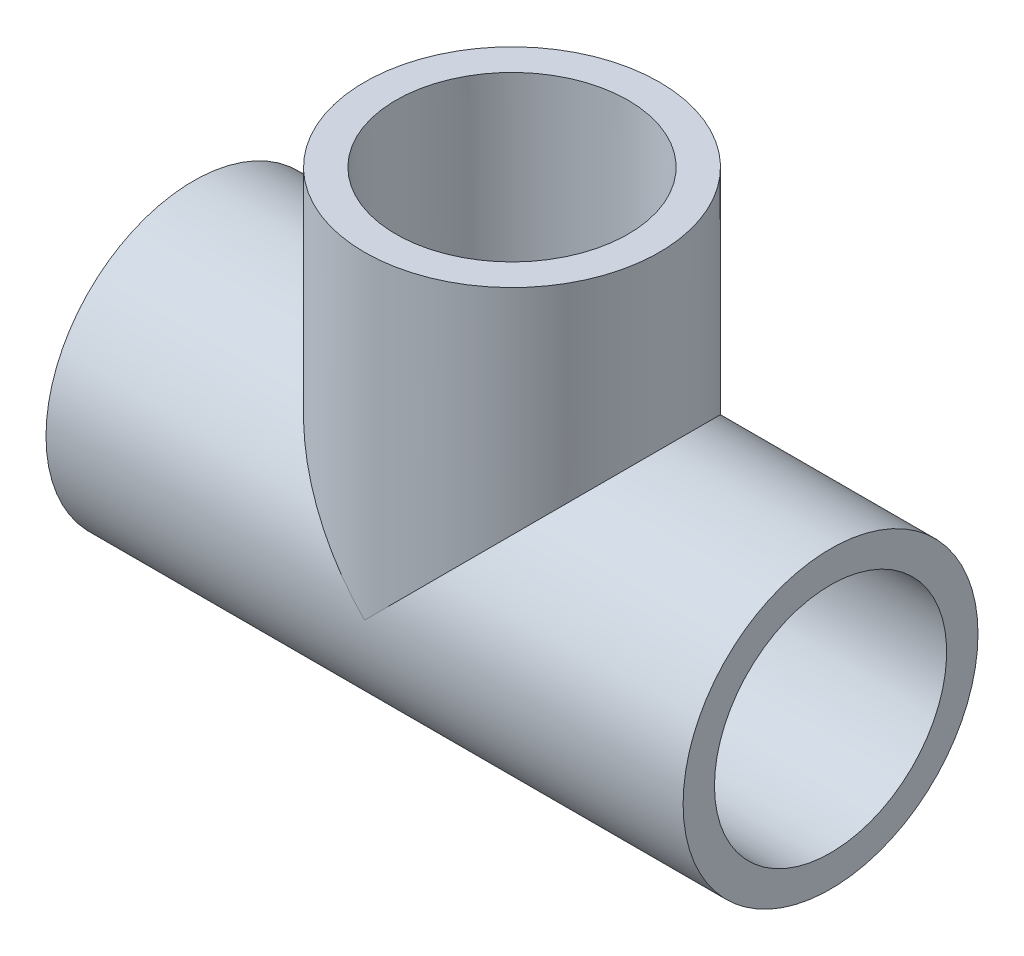
SolidWorks part; units mm, degrees
ref_plane "Front Plane" through (0, 0, 0) normal (0, 0, 1) x (1, 0, 0)
ref_plane "Top Plane" through (0, 0, 0) normal (0, 1, 0) x (1, 0, 0)
ref_plane "Right Plane" through (0, 0, 0) normal (1, 0, 0) x (0, 0, -1)
sketch "Sketch0" plane through (0, 0, 0) normal (0, 0, 1) x (1, 0, 0)
  line L0 (-46.1772, 0) -> (0, 0) construction
  line L1 (0, 0) -> (0, 46.1772) construction
  line L2 (-17.4752, 0) -> (0, 0) construction
  line L3 (0, 0) -> (0, 17.4752) construction
  line L4 (-46.1772, 21.3741) -> (-46.1772, -21.3741) construction
  line L5 (-17.4752, 16.637) -> (-46.1772, 16.8275) construction
  line L6 (-17.4752, 16.637) -> (-17.4752, -16.637) construction
  line L7 (-17.4752, -16.637) -> (-46.1772, -16.8275) construction
  line L8 (-46.1772, 16.8275) -> (-46.1772, -16.8275) construction
  line L9 (-21.3741, 46.1772) -> (21.3741, 46.1772) construction
  line L10 (-16.8275, 46.1772) -> (16.8275, 46.1772) construction
  line L11 (16.8275, 46.1772) -> (16.637, 17.4752) construction
  line L12 (16.637, 17.4752) -> (-16.637, 17.4752) construction
  line L13 (-16.637, 17.4752) -> (-16.8275, 46.1772) construction
  line L14 (-17.4752, 12.1539) -> (-17.4752, -12.1539) construction
  line L18 (-12.1539, 17.4752) -> (12.1539, 17.4752) construction
  dimension "H" = 46.1772
  dimension "G" = 17.4752
  dimension "M" = 42.7482
  dimension "OD A" = 33.655
  dimension "OD B" = 33.274
  dimension "ID" = 24.3078
sketch "Sketch1" plane through (0, 0, 0) normal (0, 0, 1) x (1, 0, 0)
  line L0 (-46.1772, 0) -> (0, 0) construction
  line L1 (-46.1772, 0) -> (0, 0) construction
  line L3 (-46.1772, -21.3741) -> (-17.4752, -21.3741)
  line L4 (-46.1772, -21.3741) -> (-46.1772, -16.8275)
  line L5 (-46.1772, -16.8275) -> (-17.4752, -16.637)
  line L6 (-17.4752, -21.3741) -> (-17.4752, -16.637)
revolve "Revolve1" add sketch "Sketch1" angle 360 about L1
mirror "Mirror1" about plane through (0, 0, 0) normal (1, 0, 0) of bodies 102
sketch "Sketch2" plane through (0, 0, 0) normal (0, 0, 1) x (1, 0, 0)
  line L0 (16.8275, 46.1772) -> (16.637, 17.4752)
  line L1 (16.637, 17.4752) -> (21.3741, 17.4752)
  line L2 (21.3741, 17.4752) -> (21.3741, 46.1772)
  line L3 (21.3741, 46.1772) -> (16.8275, 46.1772)
  line L4 (0, 0) -> (0, 46.1772) construction
  line L5 (0, 0) -> (0, 46.1772) construction
revolve "Revolve2" add sketch "Sketch2" angle 360 about L5
sketch "Sketch3" plane through (-17.4752, 0, 0) normal (1, 0, 0) x (0, 0, -1)
  line L0 (-21.3741, 17.4752) -> (21.3741, 17.4752) construction
  line L2 (12.3073, 17.4752) -> (-12.3073, 17.4752)
  circle A1 centre (0, 0) radius 21.3741 construction
  arc A3 (-12.3073, 17.4752) -> (12.3073, 17.4752) centre (0, 0) ccw
extrude "Boss-Extrude1" add sketch "Sketch3" along normal up to surface (34.9504 mm away) up to face at (17.4752, 0, 16.637)
sketch "Sketch4" plane through (0, 17.4752, 0) normal (0, -1, 0) x (1, 0, 0)
  line L0 (17.4752, -12.3073) -> (17.4752, 12.3073)
  line L1 (-17.4752, -12.3073) -> (-17.4752, 12.3073)
  circle A0 centre (0, 0) radius 21.3741 construction
  arc A1 (17.4752, 12.3073) -> (-17.4752, 12.3073) centre (0, 0) ccw
  arc A2 (-17.4752, -12.3073) -> (17.4752, -12.3073) centre (0, 0) ccw
  circle A3 centre (0, 0) radius 21.3741 construction
  circle A4 centre (0, 0) radius 21.3741 construction
extrude "Boss-Extrude2" add sketch "Sketch4" along normal up to surface (17.4752 mm away) up to plane "Top Plane"
sketch "Sketch5" plane through (-17.4752, 0, 0) normal (-1, 0, 0) x (0, 0, 1)
  line L0 (0, 16.637) -> (0, -16.637) construction
  circle A0 centre (0, 0) radius 12.1539
extrude "Cut-Extrude1" cut sketch "Sketch5" against normal up to surface (34.9504 mm away) up to face at (17.4752, 0, 16.637)
sketch "Sketch6" plane through (0, 17.4752, 0) normal (0, 1, 0) x (1, 0, 0)
  circle A0 centre (0, 0) radius 12.1539
extrude "Cut-Extrude2" cut sketch "Sketch6" against normal up to vertex (17.4752 mm away) up to point (0, 0, 0)
